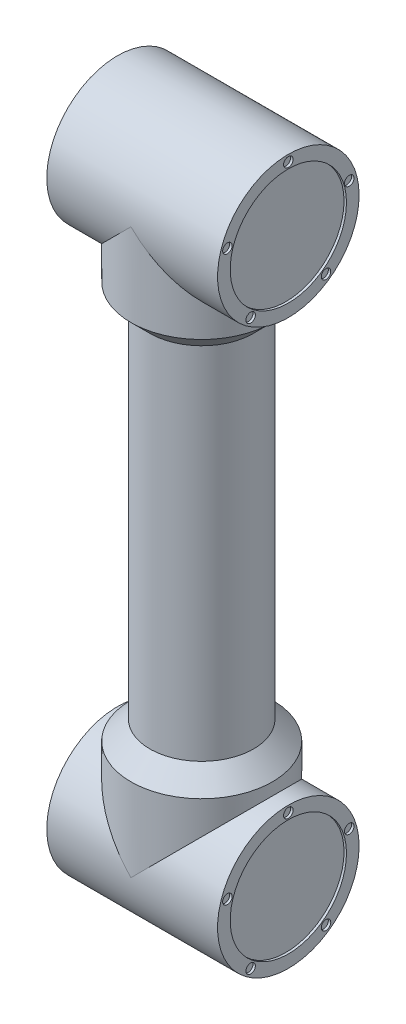
SolidWorks part; units mm, degrees
ref_plane "Alzado" through (0, 0, 0) normal (0, 0, 1) x (1, 0, 0)
ref_plane "Planta" through (0, 0, 0) normal (0, 1, 0) x (1, 0, 0)
ref_plane "Vista lateral" through (0, 0, 0) normal (1, 0, 0) x (0, 0, -1)
sketch "Croquis2" plane through (0, 0, 0) normal (0, 0, 1) x (1, 0, 0)
  line L0 (0, 0) -> (-58, 0)
  line L1 (-58, 0) -> (-58, 68)
  line L2 (-58, 68) -> (-42.5, 83.5794)
  line L3 (-42.5, 83.5794) -> (-42.5, 378.5794)
  line L4 (-42.5, 378.5794) -> (-58, 394.0004)
  line L5 (-58, 394.0004) -> (-58, 462.0004)
  line L6 (-58, 462.0004) -> (0, 462.0004)
  line L7 (0, 462.0004) -> (0, 0)
  point P3 (-100.5645, 596.2802)
  point P10 (-100.5645, 518.0228)
  point P11 (-58, 401.0083)
  point P12 (-42.5, 378.5794)
  dimension "D1" = 295
  dimension "D3" = 58
  dimension "D4" = 58
  dimension "D5" = 42.5
  dimension "D6" = 68
  dimension "D7" = 68
revolve "Revolución1" add sketch "Croquis2" angle 360 about L7
sketch "Croquis3" plane through (0, 0, 0) normal (1, 0, 0) x (0, 0, -1)
  line L0 (58, 462.0004) -> (-58, 462.0004) construction
  circle A0 centre (0, 462.0004) radius 58
  circle A1 centre (0, 0) radius 58
  dimension "D1" = 116
  dimension "D2" = 116
extrude "Saliente-Extruir2" add sketch "Croquis3" along normal blind 69 and the other way blind 69
sketch "Croquis5" plane through (69, 0, 0) normal (1, 0, 0) x (0, 0, -1)
  circle A0 centre (0, 0) radius 58
  circle A1 centre (0, 0) radius 47.653
  circle A2 centre (0, 52.5263) radius 3.8957
  circle A3 centre (49.9555, 16.2315) radius 3.8957
  circle A4 centre (30.8742, -42.4947) radius 3.8957
  circle A5 centre (-30.8742, -42.4947) radius 3.8957
  circle A6 centre (-49.9555, 16.2315) radius 3.8957
  circle A7 centre (0, 462.0004) radius 47.653
  circle A8 centre (0, 462.0004) radius 58
  circle A9 centre (-49.9555, 478.2319) radius 3.8957
  circle A10 centre (0, 514.5267) radius 3.8957
  circle A11 centre (30.8742, 419.5057) radius 3.8957
  circle A12 centre (-30.8742, 419.5057) radius 3.8957
  circle A13 centre (49.9555, 476.2315) radius 3.8957
  point P17 (0, 0)
  dimension "D2" = 2
  dimension "D3" = 2
  dimension "D1" = 5
extrude "Saliente-Extruir3" add sketch "Croquis5" along normal blind 2
